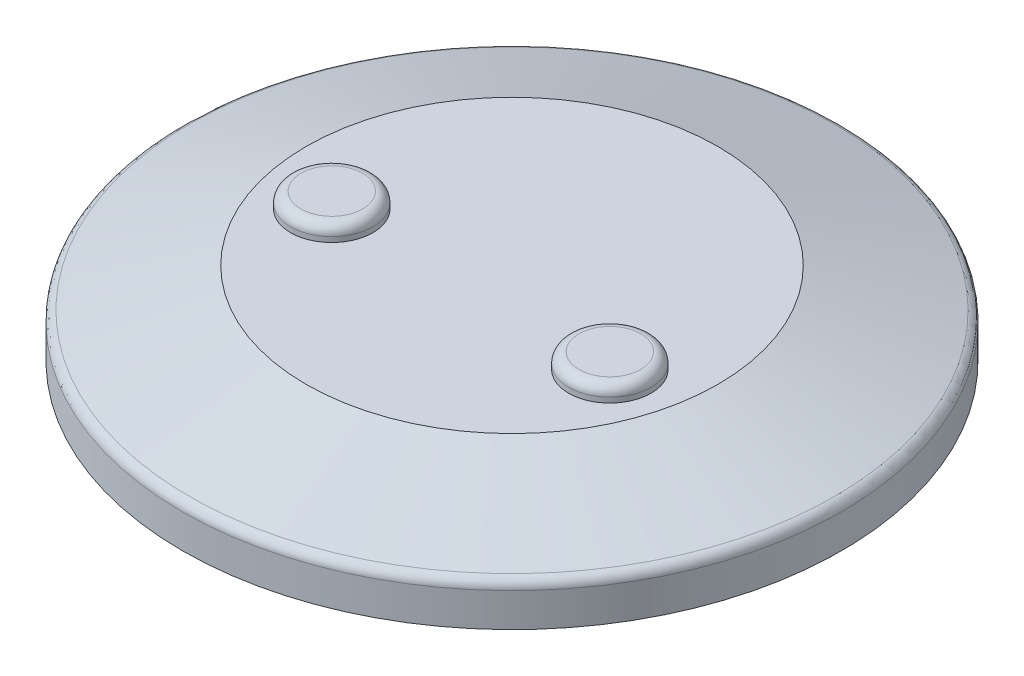
SolidWorks part; units mm, degrees
material "1060 Alloy"
ref_plane "Front Plane" through (0, 0, 0) normal (0, 0, 1) x (1, 0, 0)
ref_plane "Top Plane" through (0, 0, 0) normal (0, 1, 0) x (1, 0, 0)
ref_plane "Right Plane" through (0, 0, 0) normal (1, 0, 0) x (0, 0, -1)
sketch "Sketch1" plane through (0, 0, 0) normal (0, 1, 0) x (1, 0, 0)
  circle A0 centre (0, 0) radius 32
  dimension "D1" = 64
extrude "Boss-Extrude1" add sketch "Sketch1" along normal blind 4
sketch "Sketch2" plane through (0, 4, 0) normal (0, 1, 0) x (1, 0, 0)
  circle A0 centre (0, 0) radius 32 construction
  circle A1 centre (0, 0) radius 32
ref_plane "Plane1" through (0, 8, 0) normal (0, 1, 0) x (-1, 0, 0)
sketch "Sketch3" plane through (0, 8, 0) normal (0, 1, 0) x (-1, 0, 0)
  circle A0 centre (0, 0) radius 20
  dimension "D1" = 40
loft "Loft1" add profiles "Sketch3", "Sketch2" connector at (5.3272, 8, -19.2775) connector at (9.6903, 4, -30.4975)
fillet "Fillet1" radius 1 1 edges at (0, 4, 32)
sketch "Sketch4" plane through (0, 8, 0) normal (0, 1, 0) x (1, 0, 0)
  line L0 (0, 20) -> (0, -20) construction
  line L1 (-13.5, -4) -> (0, -4) construction
  line L2 (0, -4) -> (13.5, -4) construction
  circle A0 centre (0, 0) radius 20 construction
  circle A1 centre (-13.5, -4) radius 4
  circle A2 centre (13.5, -4) radius 4
  circle A3 centre (0, 0) radius 32 construction
  dimension "D1" = 8
  dimension "D2" = 27
  dimension "D3" = 4
extrude "Boss-Extrude2" add sketch "Sketch4" along normal blind 1.5
fillet "Fillet2" radius 1 2 edges at (-13.5, 9.5, 8) (13.5, 9.5, 8)
ref_plane "Plane2" through (0, 0, 4) normal (0, 0, 1) x (1, 0, 0)
ref_axis "Axis2" through (0, 9.975, 4) along (0, -1, 0)
sketch "Sketch5" plane through (0, 8, 0) normal (0, 1, 0) x (1, 0, 0)
  line L0 (0, -4) -> (-19.6157, -7.9018) construction
  line L1 (0, -4) -> (7.6537, 14.4776) construction
  line L2 (0, -4) -> (-20, -4) construction
  line L3 (0, -4) -> (0, 16) construction
  arc A0 (7.6537, 14.4776) -> (-19.6157, -7.9018) centre (0, -4) ccw
  dimension "D3" = 20
  dimension "D1" = 11.25
  dimension "D2" = 22.5
